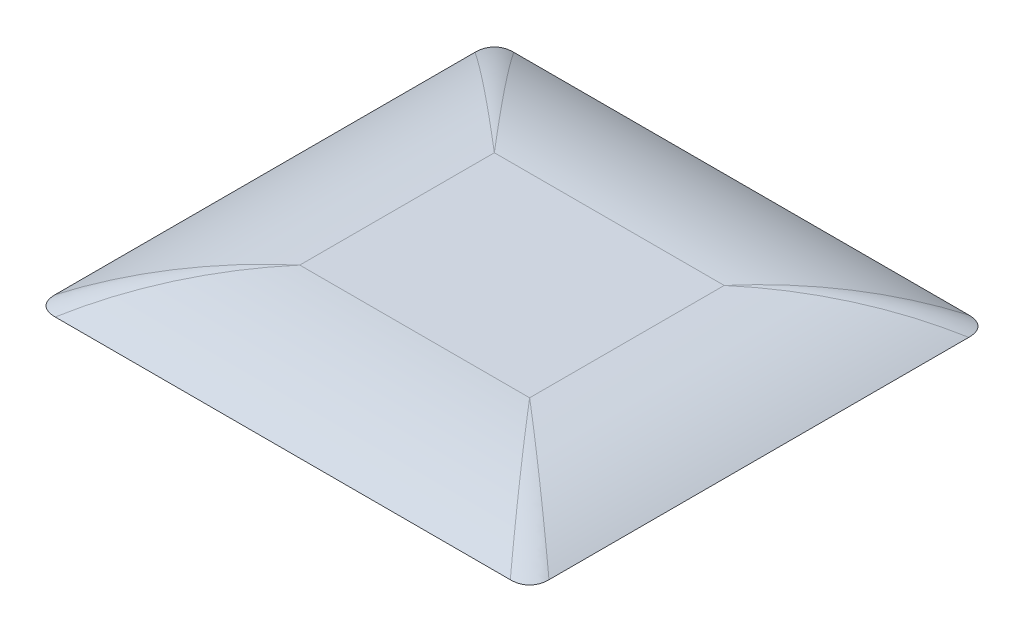
SolidWorks part; units mm, degrees
ref_plane "Front Plane" through (0, 0, 0) normal (0, 0, 1) x (1, 0, 0)
ref_plane "Top Plane" through (0, 0, 0) normal (0, 1, 0) x (1, 0, 0)
ref_plane "Right Plane" through (0, 0, 0) normal (1, 0, 0) x (0, 0, -1)
sketch "Sketch1" plane through (0, 0, 0) normal (0, 1, 0) x (1, 0, 0)
  line L1 (-81.6184, 61.8734) -> (58.3816, 61.8734)
  line L2 (-81.6184, 61.8734) -> (-81.6184, -68.1266)
  line L3 (-81.6184, -68.1266) -> (58.3816, -68.1266)
  line L4 (58.3816, 61.8734) -> (58.3816, -68.1266)
  dimension "D1" = 130
  dimension "D2" = 140
extrude "Boss-Extrude1" add sketch "Sketch1" along normal blind 10
fillet "Fillet1" radius 75 4 edges at (-11.6184, 10, -61.8734) (58.3816, 10, 3.1266) (-11.6184, 10, 68.1266) (-81.6184, 10, 3.1266)
fillet "Fillet6" radius 11 1 edges at (-63.5667, 7.4569, -43.8217)
fillet "Fillet7" radius 11 3 edges at (40.33, 7.4569, 50.0749) (40.33, 7.4569, -43.8217) (-63.5667, 7.4569, 50.0749)
